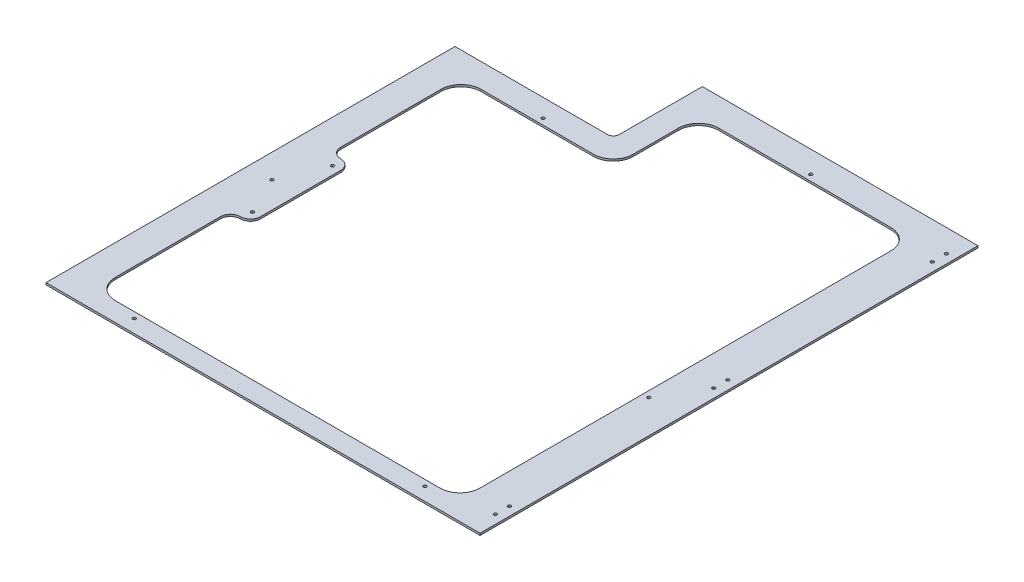
SolidWorks part; units mm, degrees
ref_plane "Alzado" through (0, 0, 0) normal (0, 0, 1) x (1, 0, 0)
ref_plane "Planta" through (0, 0, 0) normal (0, 1, 0) x (1, 0, 0)
ref_plane "Vista lateral" through (0, 0, 0) normal (1, 0, 0) x (0, 0, -1)
sketch "Croquis1" plane through (0, 0, 0) normal (0, 1, 0) x (1, 0, 0)
  line L1 (0, 0) -> (434, 0)
  line L2 (0, 0) -> (0, 500)
  line L3 (0, 500) -> (434, 500)
  line L4 (434, 0) -> (434, 500)
  dimension "D1" = 500
  dimension "D2" = 434
extrude "Saliente-Extruir1" add sketch "Croquis1" along normal blind 2
sketch "Croquis3" plane through (0, 0, 0) normal (0, -1, 0) x (1, 0, 0)
  line L1 (0, -500) -> (157, -500)
  line L2 (0, -500) -> (0, -410)
  line L3 (0, -410) -> (157, -410)
  line L4 (157, -500) -> (157, -410)
  dimension "D1" = 90
  dimension "157" = 157
extrude "Cortar-Extruir2" cut sketch "Croquis3" against normal up to surface (2 mm away) up to face at (217, 2, -250)
fillet "Redondeo1" radius 5 1 edges at (157, 1, -410)
sketch "Croquis4" plane through (0, 0, 0) normal (0, -1, 0) x (1, 0, 0)
  line L0 (434, 0) -> (434, -500) construction
  line L1 (30, -20) -> (394, -20)
  line L2 (30, -20) -> (30, -385)
  line L3 (30, -385) -> (182, -385)
  line L4 (394, -20) -> (394, -233.6615)
  line L6 (182, -385) -> (182, -470)
  line L7 (182, -470) -> (394, -470)
  line L8 (394, -233.6615) -> (394, -470)
  line L9 (434, -500) -> (157, -500) construction
  line L10 (0, 0) -> (434, 0) construction
  line L11 (0, -410) -> (0, 0) construction
  line L12 (152, -410) -> (0, -410) construction
  line L13 (157, -500) -> (157, -415) construction
  dimension "D1" = 40
  dimension "D2" = 30
  dimension "D3" = 20
  dimension "D4" = 30
  dimension "D5" = 25
  dimension "D6" = 25
extrude "Cortar-Extruir3" cut sketch "Croquis4" against normal up to surface (2 mm away) up to face at (190.7194, 2, -319.1378)
fillet "Redondeo2" radius 20 6 edges at (30, 1, -385) (182, 1, -385) (182, 1, -470) (394, 1, -470) (394, 1, -20) (30, 1, -20)
sketch "Croquis6" plane through (0, 0, 0) normal (0, -1, 0) x (1, 0, 0)
  line L0 (374, -20) -> (50, -20) construction
  line L1 (0, -410) -> (0, 0) construction
  line L2 (288, -470) -> (288, -243.2159) construction
  line L3 (202, -470) -> (374, -470) construction
  line L4 (106, -385) -> (106, -410) construction
  line L5 (30, -202.5) -> (394, -202.5) construction
  line L6 (30, -40) -> (30, -365) construction
  line L7 (394, -450) -> (394, -40) construction
  line L8 (50, -385) -> (162, -385) construction
  line L9 (152, -410) -> (0, -410) construction
  circle A0 centre (75, -14) radius 1.55
  circle A1 centre (365, -14) radius 1.55
  circle A2 centre (288, -476) radius 1.55
  circle A5 centre (106, -391) radius 1.55
  circle A6 centre (24, -202.5) radius 1.55
  circle A7 centre (400, -202.5) radius 1.55
  point P15 (106, -392.3879)
  dimension "D1" = 3.1
  dimension "D5" = 3.1
  dimension "D2" = 6
  dimension "D3" = 290
  dimension "D4" = 75
  dimension "D6" = 6
  dimension "D7" = 6
  dimension "D8" = 6
  dimension "D9" = 6
extrude "Cortar-Extruir5" cut sketch "Croquis6" against normal up to surface (2 mm away) up to face at (202, 2, -291.6667)
sketch "Croquis7" plane through (0, 0, 0) normal (0, -1, 0) x (1, 0, 0)
  line L0 (0, 0) -> (434, 0) construction
  line L2 (434, 0) -> (434, -500) construction
  line L3 (434, -500) -> (157, -500) construction
  line L4 (434, -250) -> (394, -250) construction
  line L5 (394, -450) -> (394, -40) construction
  circle A0 centre (424.25, -25) radius 1.55
  circle A1 centre (424.25, -39) radius 1.55
  circle A2 centre (424.25, -475) radius 1.55
  circle A3 centre (424.25, -461) radius 1.55
  circle A4 centre (424.25, -243) radius 1.55
  circle A5 centre (424.25, -257) radius 1.55
  dimension "D1" = 3.1
  dimension "D2" = 14
  dimension "D3" = 25
  dimension "D4" = 9.75
  dimension "D5" = 14
  dimension "D6" = 9.75
  dimension "D7" = 25
  dimension "D8" = 7
  dimension "D9" = 7
extrude "Cortar-Extruir6" cut sketch "Croquis7" against normal up to surface (2 mm away) up to face at (400, 2, -204.05)
sketch "Croquis8" plane through (0, 0, 0) normal (0, -1, 0) x (1, 0, 0)
  line L0 (0, -205) -> (136.8226, -205) construction
  line L1 (0, -410) -> (0, 0) construction
  line L2 (30, -40) -> (30, -365) construction
  line L3 (30, -155) -> (50, -155)
  line L4 (30, -155) -> (30, -255)
  line L5 (30, -255) -> (50, -255)
  line L6 (50, -155) -> (50, -255)
  dimension "D1" = 100
  dimension "D2" = 50
  dimension "D3" = 20
extrude "Saliente-Extruir2" add sketch "Croquis8" against normal up to surface (2 mm away) up to face at (424.25, 2, -26.55)
fillet "Redondeo3" radius 10 4 edges at (30, 1, -255) (50, 1, -255) (50, 1, -155) (30, 1, -155)
sketch "Croquis9" plane through (0, 0, 0) normal (0, -1, 0) x (1, 0, 0)
  line L0 (0, -205) -> (50, -205) construction
  line L1 (0, -410) -> (0, 0) construction
  line L2 (50, -245) -> (50, -165) construction
  circle A0 centre (42, -165) radius 1.55
  circle A1 centre (42, -245) radius 1.55
  dimension "D2" = 3.1
  dimension "D1" = 40
  dimension "D3" = 40
  dimension "D4" = 8
  dimension "D5" = 8
extrude "Cortar-Extruir7" cut sketch "Croquis9" against normal up to surface (2 mm away) up to face at (424.25, 2, -26.55)
sketch "Croquis10" plane through (0, 0, 0) normal (0, -1, 0) x (1, 0, 0)
  line L12 (1, -409) -> (152, -409)
  line L13 (158, -415) -> (158, -499)
  line L14 (158, -499) -> (433, -499)
  line L15 (433, -499) -> (433, -1)
  line L16 (433, -1) -> (1, -1)
  line L17 (1, -1) -> (1, -409)
  line L18 (1, -409) -> (152, -409)
  line L19 (158, -415) -> (158, -499)
  line L20 (158, -499) -> (433, -499)
  line L21 (433, -499) -> (433, -1)
  line L22 (433, -1) -> (1, -1)
  line L23 (1, -1) -> (1, -409)
  arc A2 (158, -415) -> (152, -409) centre (152, -415) ccw
  arc A3 (158, -415) -> (152, -409) centre (152, -415) ccw
  dimension "D1" = 1
extrude "Cortar-Extruir8" cut sketch "Croquis10" against normal blind 10 flip side to cut
sketch "Croquis11" plane through (0, 0, 0) normal (0, -1, 0) x (1, 0, 0)
  line L0 (433, -499) -> (433, -1) construction
  line L1 (158, -499) -> (433, -499)
  line L2 (158, -499) -> (158, -497.75)
  line L3 (158, -497.75) -> (433, -497.75)
  line L4 (433, -499) -> (433, -497.75)
  dimension "D1" = 1.25
extrude "Cortar-Extruir9" cut sketch "Croquis11" against normal up to surface (2 mm away) up to face at (148, 2, -262.7778)
sketch "Croquis12" plane through (0, 0, 0) normal (0, -1, 0) x (1, 0, 0)
  line L1 (1, -1) -> (0, -1)
  line L2 (1, -1) -> (1, -409)
  line L3 (1, -409) -> (0, -409)
  line L4 (0, -1) -> (0, -409)
  dimension "D1" = 1
extrude "Saliente-Extruir3" add sketch "Croquis12" against normal up to surface (2 mm away) up to face at (148, 2, -262.7778)
sketch "Croquis13" plane through (0, 0, 0) normal (0, -1, 0) x (1, 0, 0)
  line L0 (394, -450) -> (394, -40) construction
  line L1 (202, -470) -> (374, -470) construction
  line L2 (182, -405) -> (182, -450) construction
  line L3 (50, -385) -> (162, -385) construction
  line L4 (30, -265) -> (30, -365) construction
  line L5 (50, -245) -> (50, -165) construction
  line L6 (30, -40) -> (30, -145) construction
  line L7 (374, -20) -> (50, -20) construction
  line L8 (394, -450) -> (394, -40)
  line L9 (202, -470) -> (374, -470)
  line L10 (182, -405) -> (182, -450)
  line L11 (50, -385) -> (162, -385)
  line L12 (30, -265) -> (30, -365)
  line L13 (50, -245) -> (50, -165)
  line L14 (30, -40) -> (30, -145)
  line L15 (374, -20) -> (50, -20)
  line L16 (374, -5) -> (50, -5)
  line L17 (15, -40) -> (15, -145)
  line L19 (15, -265) -> (15, -365)
  line L20 (50, -400) -> (162, -400)
  line L21 (167, -405) -> (167, -450)
  line L22 (202, -485) -> (374, -485)
  line L23 (409, -450) -> (409, -40)
  line L24 (15, -145) -> (15, -265)
  line L26 (35, -240.5051) -> (35, -169.4949) construction
  arc A0 (394, -40) -> (374, -20) centre (374, -40) ccw construction
  arc A1 (374, -470) -> (394, -450) centre (374, -450) ccw construction
  arc A2 (182, -450) -> (202, -470) centre (202, -450) ccw construction
  arc A3 (182, -405) -> (162, -385) centre (162, -405) ccw construction
  arc A4 (30, -365) -> (50, -385) centre (50, -365) ccw construction
  arc A5 (40, -255) -> (30, -265) centre (40, -265) ccw construction
  arc A6 (40, -255) -> (50, -245) centre (40, -245) ccw construction
  arc A7 (50, -165) -> (40, -155) centre (40, -165) ccw construction
  arc A8 (30, -145) -> (40, -155) centre (40, -145) ccw construction
  arc A9 (50, -20) -> (30, -40) centre (50, -40) ccw construction
  arc A10 (394, -40) -> (374, -20) centre (374, -40) ccw
  arc A11 (374, -470) -> (394, -450) centre (374, -450) ccw
  arc A12 (182, -450) -> (202, -470) centre (202, -450) ccw
  arc A13 (182, -405) -> (162, -385) centre (162, -405) ccw
  arc A14 (30, -365) -> (50, -385) centre (50, -365) ccw
  arc A15 (40, -255) -> (30, -265) centre (40, -265) ccw
  arc A16 (40, -255) -> (50, -245) centre (40, -245) ccw
  arc A17 (50, -165) -> (40, -155) centre (40, -165) ccw
  arc A18 (30, -145) -> (40, -155) centre (40, -145) ccw
  arc A19 (50, -20) -> (30, -40) centre (50, -40) ccw
  arc A20 (50, -5) -> (15, -40) centre (50, -40) ccw
  circle A21 centre (42, -165) radius 5
  arc A22 (35, -169.4949) -> (35, -169.4949) centre (35, -169.4949) ccw
  arc A23 (35, -240.5051) -> (35, -240.5051) centre (35, -240.5051) ccw
  circle A24 centre (42, -245) radius 5
  arc A25 (15, -365) -> (50, -400) centre (50, -365) ccw
  arc A26 (167, -405) -> (162, -400) centre (162, -405) ccw
  arc A27 (167, -450) -> (202, -485) centre (202, -450) ccw
  arc A28 (374, -485) -> (409, -450) centre (374, -450) ccw
  arc A29 (409, -40) -> (374, -5) centre (374, -40) ccw
  arc A30 (15, -145) -> (35, -169.4949) centre (40, -145) ccw construction
  arc A31 (35, -240.5051) -> (15, -265) centre (40, -265) ccw construction
  circle A32 centre (24, -202.5) radius 2.25
  circle A33 centre (75, -14) radius 2.25
  circle A34 centre (365, -14) radius 2.25
  circle A35 centre (400, -202.5) radius 2.25
  circle A36 centre (288, -476) radius 2.25
  circle A37 centre (106, -391) radius 2.25
  dimension "D2" = 10
  dimension "D3" = 10
  dimension "D4" = 4.5
  dimension "D1" = 15
